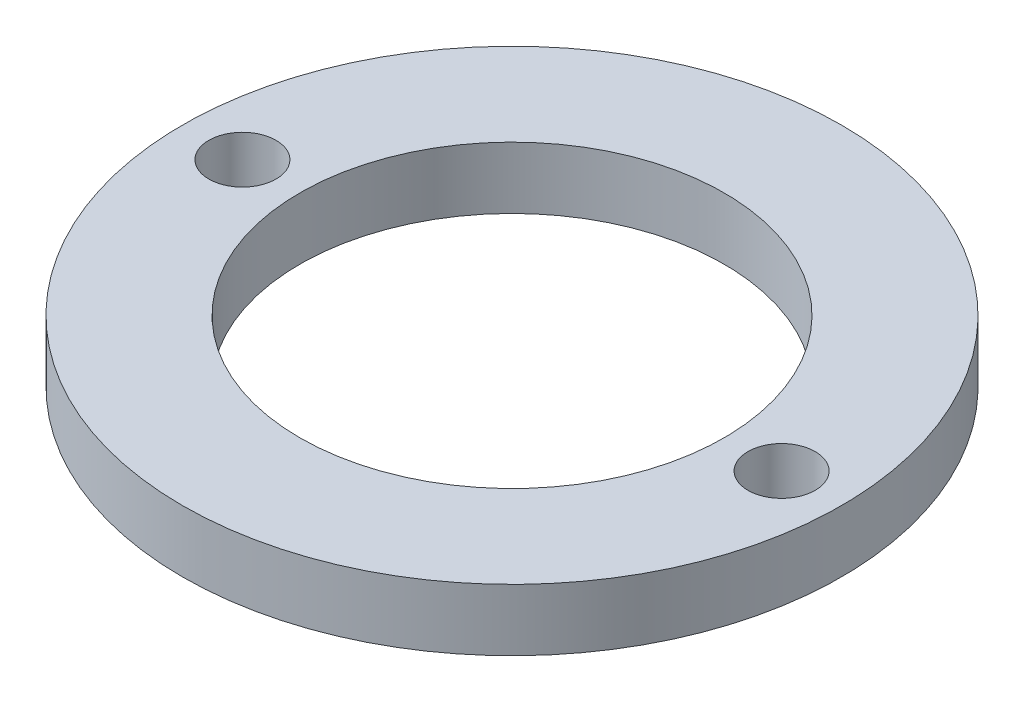
SolidWorks part; units mm, degrees
material "Acrylic (Medium-high impact)"
ref_plane "Front Plane" through (0, 0, 0) normal (0, 0, 1) x (1, 0, 0)
ref_plane "Top Plane" through (0, 0, 0) normal (0, 1, 0) x (1, 0, 0)
ref_plane "Right Plane" through (0, 0, 0) normal (1, 0, 0) x (0, 0, -1)
sketch "Sketch1" plane through (0, 0, 0) normal (0, 1, 0) x (1, 0, 0)
  circle A0 centre (0, 0) radius 16
  circle A1 centre (0, 0) radius 10.3
  dimension "D1" = 32
  dimension "D2" = 20.6
extrude "Boss-Extrude1" add sketch "Sketch1" along normal blind 3
hole_wizard "#4 Clearance Hole1" positions "Sketch6" profile "Sketch3" hole size "#4" standard "ANSI Inch" end condition through all
sketch "Sketch6" plane through (0, 3, 0) normal (0, 1, 0) x (1, 0, 0)
  point P0 (-13.0875, 0)
  point P2 (13.0875, 0)
  dimension "D2" = 13.0875
  dimension "D4" = 13.0875
sketch "Sketch3" plane through (-13.0875, 3, 0) normal (1, 0, 0) x (0, 0, 1)
  line L0 (0, 0) -> (0, 3)
  line L1 (0, 3) -> (1.6319, 3)
  line L2 (1.6319, 3) -> (1.6319, 0)
  line L5 (1.6319, 0) -> (0, 0)
  line L11 (0, -6.35) -> (0, 107.95) construction
  dimension "Thru Hole Dia." = 3.2639
  dimension "Thru Hole Depth" = 3
equation "\"D4@Sketch6\"=\"D2@Sketch6\""
